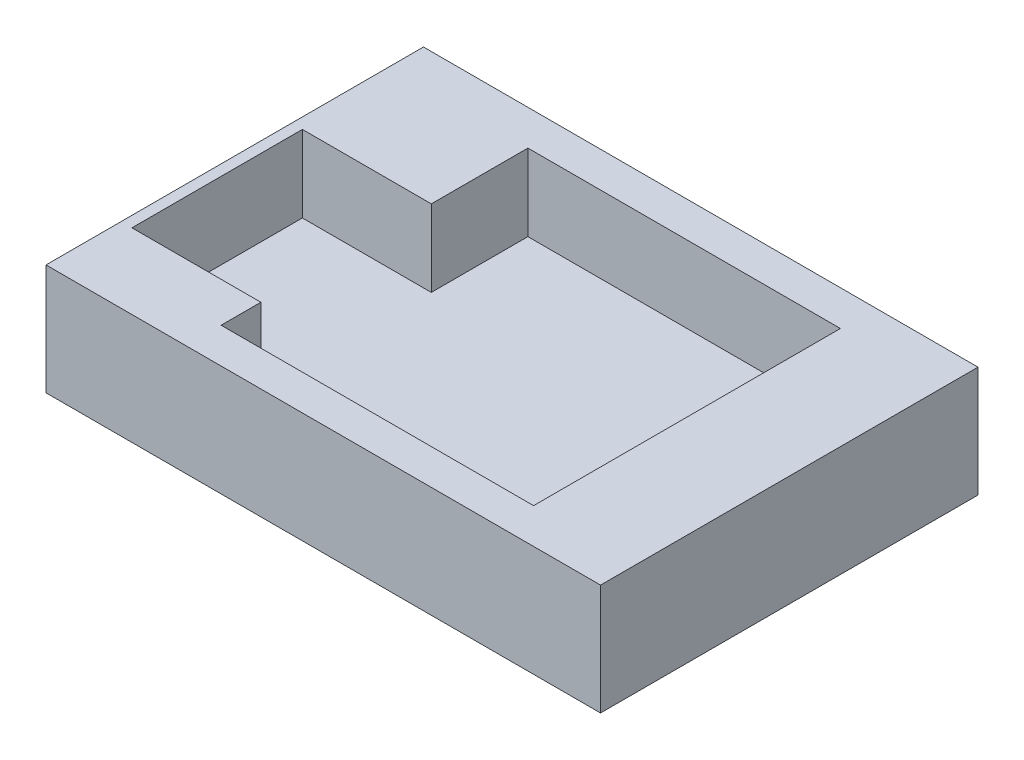
SolidWorks part; units mm, degrees
material "ABS"
ref_plane "Front Plane" through (0, 0, 0) normal (0, 0, 1) x (1, 0, 0)
ref_plane "Top Plane" through (0, 0, 0) normal (0, 1, 0) x (1, 0, 0)
ref_plane "Right Plane" through (0, 0, 0) normal (1, 0, 0) x (0, 0, -1)
sketch "Sketch1" plane through (0, 0, 0) normal (0, 1, 0) x (1, 0, 0)
  line L1 (48.8, 33.2187) -> (-48.8, 33.2187)
  line L2 (48.8, 33.2187) -> (48.8, -33.2187)
  line L3 (48.8, -33.2187) -> (-48.8, -33.2187)
  line L4 (-48.8, 33.2187) -> (-48.8, -33.2187)
  line L5 (48.8, 33.2187) -> (-48.8, -33.2187) construction
  line L6 (48.8, -33.2187) -> (-48.8, 33.2187) construction
  point P0 (0, 0)
  dimension "D1" = 97.6
  dimension "D2" = 66.4375
extrude "Boss-Extrude1" add sketch "Sketch1" along normal blind 6
sketch "Sketch3" plane through (0, 6, 0) normal (0, 1, 0) x (1, 0, 0)
  line L0 (48.8, -33.2187) -> (48.8, 33.2187) construction
  line L1 (30.8, 27) -> (-24.2, 27)
  line L2 (30.8, 27) -> (30.8, -27)
  line L3 (30.8, -27) -> (-24.2, -27)
  line L4 (-24.2, 27) -> (-24.2, -27)
  line L5 (30.8, 27) -> (-24.2, -27) construction
  line L6 (30.8, -27) -> (-24.2, 27) construction
  point P0 (3.3, 0)
  dimension "D1" = 54
  dimension "D2" = 55
  dimension "D3" = 0
  dimension "D4" = 18
sketch "Sketch4" plane through (0, 6, 0) normal (0, 1, 0) x (1, 0, 0)
  line L0 (30.8, -27) -> (30.8, -33.2187)
  line L1 (-48.8, -33.2187) -> (48.8, -33.2187) construction
  line L2 (30.8, -33.2187) -> (30.8, 33.2187)
  line L3 (48.8, 33.2187) -> (-48.8, 33.2187) construction
  line L4 (30.8, 33.2187) -> (30.8, 27)
  line L5 (30.8, 27) -> (48.8, 27)
  line L6 (48.8, -33.2187) -> (48.8, 33.2187) construction
  line L7 (48.8, 27) -> (-48.8, 27)
  line L8 (-48.8, 33.2187) -> (-48.8, -33.2187) construction
  line L9 (-48.8, 27) -> (-24.2, 27)
  line L10 (-24.2, 27) -> (-24.2, 33.2187)
  line L11 (-24.2, 33.2187) -> (-24.2, -33.2187)
  line L13 (-24.2, -33.2187) -> (-48.8, -33.2187)
  line L14 (-24.2, -33.2187) -> (-24.2, 33.2187)
  line L15 (-24.2, 33.2187) -> (-48.8, 33.2187)
  line L16 (-48.8, -33.2187) -> (-48.8, 33.2187)
  line L17 (-48.8, 33.2187) -> (48.8, 33.2187)
  line L18 (-48.8, 33.2187) -> (-48.8, 27)
  line L19 (-48.8, 27) -> (48.8, 27)
  line L20 (48.8, 33.2187) -> (48.8, 27)
  line L21 (48.8, 33.2187) -> (30.8, 33.2187)
  line L22 (48.8, 33.2187) -> (48.8, -33.2187)
  line L23 (48.8, -33.2187) -> (30.8, -33.2187)
  line L24 (30.8, 33.2187) -> (30.8, -33.2187)
  line L25 (48.8, -33.2187) -> (-48.8, -33.2187)
  line L26 (48.8, -33.2187) -> (48.8, -27)
  line L27 (48.8, -27) -> (-48.8, -27)
  line L28 (-48.8, -33.2187) -> (-48.8, -27)
  line M1 (-48.8, 33.2187) -> (-48.8, -33.2187)
  line M2 (-48.8, -33.2187) -> (48.8, -33.2187)
  line M3 (48.8, -33.2187) -> (48.8, 33.2187)
  line M4 (48.8, 33.2187) -> (-48.8, 33.2187)
extrude "Boss-Extrude2" add sketch "Sketch4" along normal blind 13.5 contours L27 L11 L7 M1 | L14 L27 L16 M2 | L0 L27 L14 M2 | L27 L0 M3 M2 | L27 L22 L5 L2 | L2 L5 M3 M4 | L7 L10 M4 M1 | L10 L7 L2 M4 region at (39.8, 6, 30.1094) region at (39.8, 6, 0) region at (3.3, 6, 30.1094) region at (3.3, 6, -30.1094) region at (39.8, 6, -30.1094) region at (-36.5, 6, 0) region at (-36.5, 6, 30.1094) region at (-36.5, 6, -30.1094)
sketch "Sketch5" plane through (0, 19.5, 0) normal (0, 1, 0) x (1, 0, 0)
  line L0 (-46.8936, -20) -> (-12.1997, -20)
  line L1 (-46.8936, -20) -> (-46.8936, 10)
  line L2 (-12.1997, -20) -> (-12.1997, 10)
  line L3 (-46.8936, 10) -> (-12.1997, 10)
  line L4 (-46.8936, -20) -> (-12.1997, 10) construction
  line L5 (-12.1997, -20) -> (-46.8936, 10) construction
  point P1 (-29.5467, -5)
  dimension "D1" = 30
  dimension "D2" = 5
extrude "Cut-Extrude1" cut sketch "Sketch5" against normal blind 13.5
